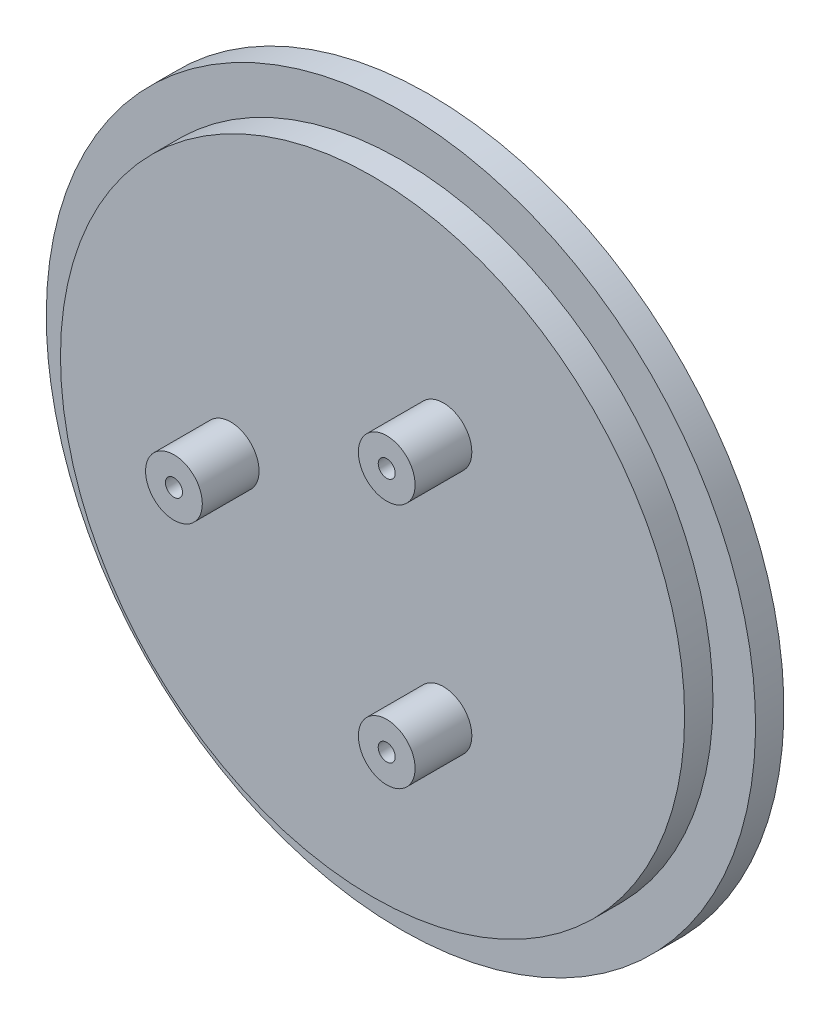
SolidWorks part; units mm, degrees
ref_plane "前视基准面" through (0, 0, 0) normal (0, 0, 1) x (1, 0, 0)
ref_plane "上视基准面" through (0, 0, 0) normal (0, 1, 0) x (1, 0, 0)
ref_plane "右视基准面" through (0, 0, 0) normal (1, 0, 0) x (0, 0, -1)
sketch "草图1" plane through (0, 0, 0) normal (0, 0, 1) x (1, 0, 0)
  circle A0 centre (0, 0) radius 22
extrude "凸台-拉伸1" add sketch "草图1" along normal blind 2
sketch "草图2" plane through (0, 0, 2) normal (0, 0, 1) x (1, 0, 0)
  circle A1 centre (-10, 0) radius 0.6
  circle A2 centre (5, -8.6603) radius 0.6
  circle A3 centre (5, 8.6603) radius 0.6
  circle A4 centre (-10, 0) radius 2
  circle A5 centre (5, 8.6603) radius 2
  circle A6 centre (5, -8.6603) radius 2
extrude "凸台-拉伸2" add sketch "草图2" along normal blind 4
sketch "草图3" plane through (0, 0, 0) normal (0, 0, -1) x (-1, 0, 0)
  circle A0 centre (0, 0) radius 25
extrude "凸台-拉伸3" add sketch "草图3" along normal blind 2
sketch "草图5" plane through (0, 0, -2) normal (0, 0, -1) x (-1, 0, 0)
  line L0 (21, -3.95) -> (21, -4)
  line L2 (21, -4) -> (29.149, -4)
  line L7 (29.149, -4) -> (29.149, 4)
  line L10 (21, -3.95) -> (21, 4)
  line L12 (29.149, 4) -> (21, 4)
extrude "切除-拉伸2" cut sketch "草图5" against normal blind 1
sketch "草图6" plane through (0, 0, -2) normal (0, 0, -1) x (-1, 0, 0)
  circle A2 centre (-18, 0) radius 5.45
  circle A3 centre (9, 15.5885) radius 5.45
  circle A4 centre (9, -15.5885) radius 5.45
  circle A5 centre (-18, 0) radius 3.85
  circle A6 centre (9, 15.5885) radius 3.85
  circle A7 centre (9, -15.5885) radius 3.85
  dimension "D1" = 3
extrude "切除-拉伸3" cut sketch "草图6" against normal blind 1.3
sketch "草图8" plane through (0, 0, 6) normal (0, 0, 1) x (1, 0, 0)
  circle A0 centre (5, -8.6603) radius 0.6
  circle A1 centre (-10, 0) radius 0.6
  circle A2 centre (5, 8.6603) radius 0.6
extrude "切除-拉伸4" cut sketch "草图8" against normal blind 18.5
sketch "草图9" plane through (0, 0, 6) normal (0, 0, 1) x (1, 0, 0)
  circle A0 centre (0, 0) radius 16.6958
extrude "切除-拉伸5" cut sketch "草图9" against normal blind 2
sketch "草图10" plane through (0, 0, -2) normal (0, 0, -1) x (-1, 0, 0)
  circle A0 centre (-5, -8.6603) radius 1.6
  circle A1 centre (-5, 8.6603) radius 1.6
extrude "切除-拉伸6" cut sketch "草图10" against normal blind 1
sketch "草图11" plane through (0, 0, -2) normal (0, 0, -1) x (-1, 0, 0)
  circle A0 centre (10, 0) radius 1.6
extrude "切除-拉伸7" cut sketch "草图11" against normal blind 3
sketch "草图13" plane through (0, 0, 4) normal (0, 0, 1) x (1, 0, 0)
  circle A0 centre (-10, 0) radius 0.6
  circle A1 centre (-10, 0) radius 2
  circle A2 centre (5, 8.6603) radius 0.6
  circle A3 centre (5, 8.6603) radius 2
  circle A4 centre (5, -8.6603) radius 0.6
  circle A5 centre (5, -8.6603) radius 2
extrude "凸台-拉伸4" add sketch "草图13" along normal blind 2
